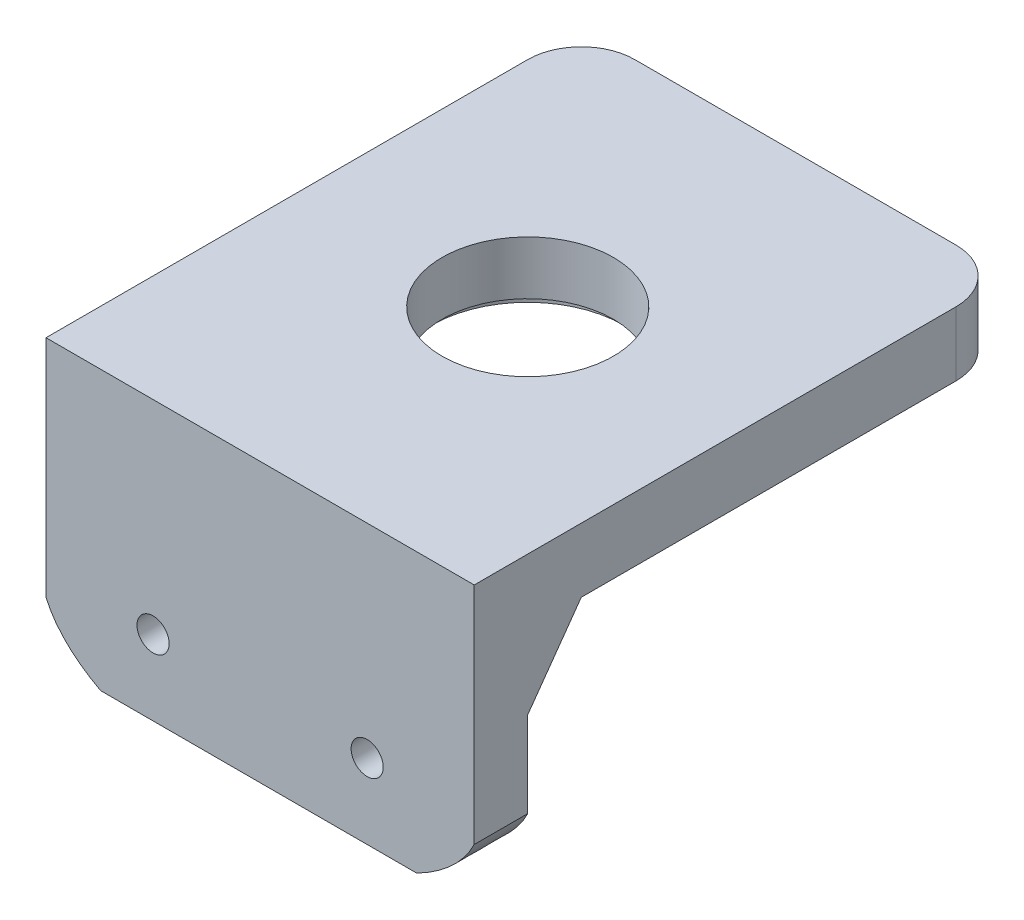
SolidWorks part; units mm, degrees
ref_plane "Front Plane" through (0, 0, 0) normal (0, 0, 1) x (1, 0, 0)
ref_plane "Top Plane" through (0, 0, 0) normal (0, 1, 0) x (1, 0, 0)
ref_plane "Right Plane" through (0, 0, 0) normal (1, 0, 0) x (0, 0, -1)
sketch "Sketch1" plane through (0, 0, 0) normal (0, 1, 0) x (1, 0, 0)
  line L1 (-20, 25) -> (20, 25)
  line L2 (-20, 25) -> (-20, -25)
  line L3 (-20, -25) -> (20, -25)
  line L4 (20, 25) -> (20, -25)
  line L5 (-20, 25) -> (20, -25) construction
  line L6 (-20, -25) -> (20, 25) construction
  point P0 (0, 0)
  dimension "D1" = 40
  dimension "D2" = 50
extrude "Boss-Extrude1" add sketch "Sketch1" along normal blind 6
sketch "Sketch3" plane through (0, 6, 0) normal (0, 1, 0) x (1, 0, 0)
  line L0 (-20, -25) -> (20, -25) construction
  circle A0 centre (0, 0) radius 8
  point P0 (0, 0)
  dimension "D2" = 16
  dimension "D1" = 25
extrude "Cut-Extrude1" cut sketch "Sketch3" against normal blind 9
sketch "Sketch4" plane through (0, 0, 0) normal (0, -1, 0) x (1, 0, 0)
  line L0 (-20, -25) -> (-20, 25) construction
  line L1 (20, 25) -> (-20, 25)
  line L2 (20, 25) -> (20, 20)
  line L3 (20, 20) -> (-20, 20)
  line L4 (-20, 25) -> (-20, 20)
  dimension "D1" = 5
extrude "Boss-Extrude2" add sketch "Sketch4" along normal blind 20
sketch "Sketch5" plane through (20, 0, 0) normal (1, 0, 0) x (0, 0, -1)
  line L0 (-20, 0) -> (25, 0) construction
  line L1 (-20, -20) -> (-20, 0) construction
  line L2 (-15, 0) -> (-20, 0)
  line L3 (-20, 0) -> (-20, -7)
  line L4 (-20, -7) -> (-15, 0)
  point P0 (-15, 0)
  point P1 (-20, -7)
  dimension "D1" = 5
  dimension "D2" = 7
extrude "Boss-Extrude3" add sketch "Sketch5" against normal blind 40
sketch "Sketch6" plane through (0, 0, 20) normal (0, 0, -1) x (-1, 0, 0)
  line L0 (-20, -20) -> (-20, -7) construction
  line L1 (20, -20) -> (20, -7) construction
  line L2 (20, -20) -> (-20, -20) construction
  circle A0 centre (-10, -13) radius 1.5
  circle A1 centre (10, -13) radius 1.5
  point P0 (10, -13)
  point P1 (-10, -13)
  dimension "D5" = 3
  dimension "D6" = 3
  dimension "D1" = 10
  dimension "D2" = 10
  dimension "D3" = 7
  dimension "D4" = 7
extrude "Cut-Extrude2" cut sketch "Sketch6" against normal through all
sketch "Sketch7" plane through (0, 6, 0) normal (0, 1, 0) x (1, 0, 0)
  line L0 (-20, 25) -> (-20, -25) construction
  line L1 (20, 25) -> (-20, 25) construction
  line L2 (20, -25) -> (20, 25) construction
  line L3 (-20, 20) -> (-20, 25)
  line L4 (-20, 25) -> (-15, 25)
  line L5 (15, 25) -> (20, 25)
  line L6 (20, 25) -> (20, 20)
  arc A0 (-15, 25) -> (-20, 20) centre (-15, 20) ccw
  arc A1 (20, 20) -> (15, 25) centre (15, 20) ccw
  point P0 (-20, 20)
  point P1 (-15, 25)
  point P4 (15, 25)
  point P7 (20, 20)
  dimension "D1" = 5
  dimension "D2" = 5
  dimension "D3" = 5
  dimension "D4" = 5
extrude "Cut-Extrude3" cut sketch "Sketch7" against normal through all
sketch "Sketch8" plane through (0, 0, 20) normal (0, 0, -1) x (-1, 0, 0)
  line L0 (-20, -20) -> (-20, -7) construction
  line L1 (20, -20) -> (-20, -20) construction
  line L2 (20, -20) -> (20, -7) construction
  line L3 (20, -15) -> (15.2918, -25.8047) construction
  line L4 (15.2918, -25.8047) -> (-14.7082, -25.8047) construction
  line L6 (-14.7082, -25.8047) -> (-20, -15) construction
  line L7 (20, -15) -> (20, -20)
  line L8 (20, -20) -> (-20, -20)
  line L9 (-20, -20) -> (-20, -15)
  spline S0 degree 3 poles (20, -15) (15.2918, -25.8047) (-14.7082, -25.8047) (-20, -15) knots 0 0 0 0 1 1 1 1
  point P0 (-20, -15)
  point P1 (-15, -20)
  point P4 (20, -15)
  point P7 (15, -20)
  line M7 (20, -20) -> (20, -7)
  line M9 (-20, -7) -> (-20, -20)
  line M10 (-20, -20) -> (20, -20)
  dimension "D1" = 5
  dimension "D2" = 5
  dimension "D3" = 5
  dimension "D4" = 5
extrude "Cut-Extrude4" cut sketch "Sketch8" against normal through all contours S0 M7 M10 | S0 M10 M9 region at (18.3865, -18.5348, 20) region at (-18.4741, -18.5485, 20)
sketch "Sketch9" plane through (0, 0, 0) normal (0, -1, 0) x (1, 0, 0)
  circle A0 centre (0, 0) radius 9
  dimension "D1" = 18
extrude "Cut-Extrude5" cut sketch "Sketch9" against normal blind 1
